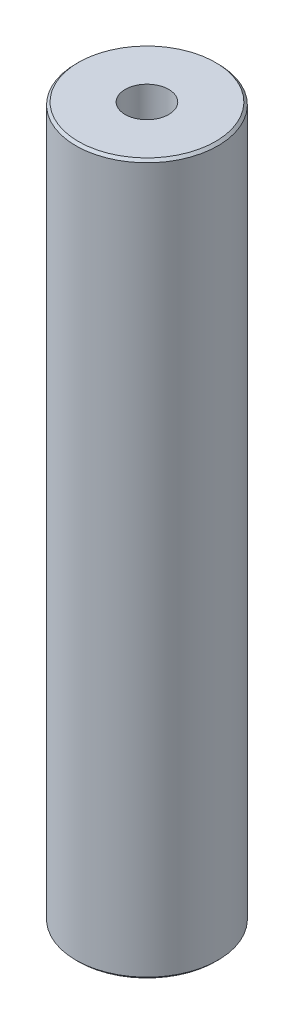
SolidWorks part; units mm, degrees
ref_plane "Front Plane" through (0, 0, 0) normal (0, 0, 1) x (1, 0, 0)
ref_plane "Top Plane" through (0, 0, 0) normal (0, 1, 0) x (1, 0, 0)
ref_plane "Right Plane" through (0, 0, 0) normal (1, 0, 0) x (0, 0, -1)
sketch "Sketch1" plane through (0, 0, 0) normal (0, 1, 0) x (1, 0, 0)
  circle A0 centre (0, 0) radius 60
  dimension "SHAFT_OD" = 120
extrude "Boss-Extrude1" add sketch "Sketch1" along normal blind 600
sketch "Sketch2" plane through (0, 0, 0) normal (0, 1, 0) x (1, 0, 0)
  circle A0 centre (0, 0) radius 18.4169
  dimension "BORE_D" = 36.8338
extrude "Cut-Extrude1" cut sketch "Sketch2" along normal through all
chamfer "Chamfer1" distance 2.0937 angle 45 2 edges at (0, 600, 60) (0, 0, 60)
